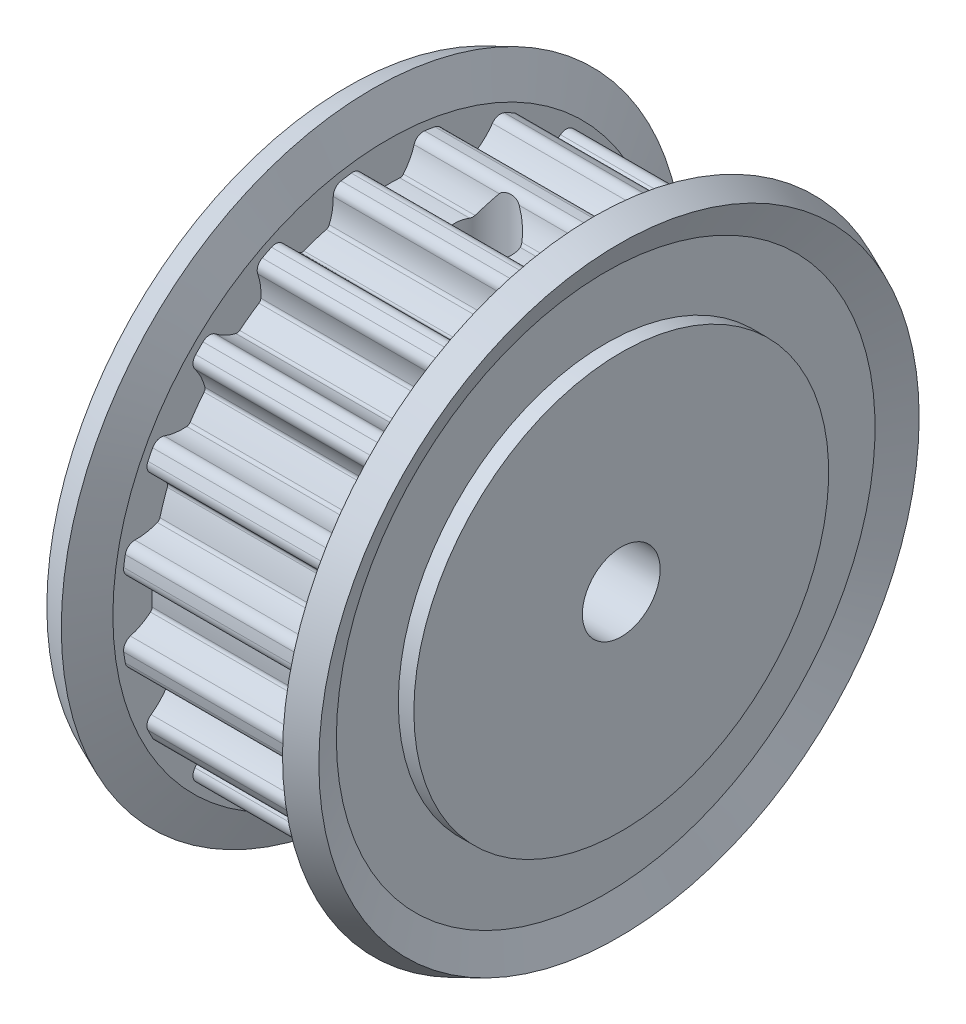
SolidWorks part; units mm, degrees
ref_plane "前视基准面" through (0, 0, 0) normal (0, 0, 1) x (1, 0, 0)
ref_plane "上视基准面" through (0, 0, 0) normal (0, 1, 0) x (1, 0, 0)
ref_plane "右视基准面" through (0, 0, 0) normal (1, 0, 0) x (0, 0, -1)
sketch "草图1" plane through (0, 0, 0) normal (0, 0, 1) x (1, 0, 0)
  line L0 (0, 12) -> (0, 2.25)
  line L1 (0, 2.25) -> (28, 2.25)
  line L2 (28, 2.25) -> (28, 4.175)
  line L3 (28, 4.175) -> (16, 4.175)
  line L4 (16, 4.175) -> (16, 12)
  line L5 (16, 12) -> (15.1, 12)
  line L6 (15.1, 12) -> (15.1, 15.5844)
  line L7 (15.1, 15.5844) -> (15.869, 17.3659)
  line L8 (15.869, 17.3659) -> (14.4, 18)
  line L9 (14.4, 18) -> (13.5, 15.915)
  line L10 (13.5, 15.915) -> (13.5, 15.435)
  line L11 (13.5, 15.435) -> (2.5, 15.435)
  line L12 (2.5, 15.435) -> (2.5, 15.915)
  line L13 (2.5, 15.915) -> (1.6, 18)
  line L14 (1.6, 18) -> (0.131, 17.3659)
  line L15 (0.131, 17.3659) -> (0.9, 15.5844)
  line L16 (0.9, 15.5844) -> (0.9, 12)
  line L17 (0.9, 12) -> (0, 12)
  line L18 (28, 0) -> (0, 0) construction
  dimension "D1" = 2.25
  dimension "D2" = 9.75
revolve "旋转1" add sketch "草图1" angle 360 about L18 reverse direction yes
sketch "草图2" plane through (0, 0, 0) normal (0, 0, 1) x (1, 0, 0)
  line L0 (16, 0) -> (16, 18)
  line L1 (16, 18) -> (32, 18)
  line L2 (32, 18) -> (32, 0)
  line L3 (32, 0) -> (16, 0)
  line L4 (32, 0) -> (16, 0) construction
revolve "切除-旋转1" cut sketch "草图2" angle 360 about L4 reverse direction yes
ref_plane "基准面1" through (2.5, 0, 0) normal (1, 0, 0) x (0, 0, -1)
sketch "草图3" plane through (2.5, 0, 0) normal (1, 0, 0) x (0, 0, -1)
  line L0 (2.1176, 15.2891) -> (2.1176, 20.58)
  line L1 (2.1176, 20.58) -> (-2.1176, 20.58)
  line L2 (-2.1176, 20.58) -> (-2.1176, 15.2891)
  arc A0 (-2.1176, 15.2891) -> (-1.5148, 14.9006) centre (-2.0421, 14.7443) cw
  arc A1 (-1.5148, 14.9006) -> (-0.8928, 13.7375) centre (1.625, 15.8318) ccw
  arc A2 (-0.8928, 13.7375) -> (-0.688, 13.6477) centre (-0.7006, 13.8974) ccw
  arc A3 (-0.688, 13.6477) -> (0.688, 13.6477) centre (0, 0) cw
  arc A4 (0.688, 13.6477) -> (0.8928, 13.7375) centre (0.7006, 13.8974) ccw
  arc A5 (0.8928, 13.7375) -> (1.5148, 14.9006) centre (-1.625, 15.8318) ccw
  arc A6 (1.5148, 14.9006) -> (2.1176, 15.2891) centre (2.0421, 14.7443) cw
extrude "切除-拉伸1" cut sketch "草图3" along normal blind 11
sketch "草图5" plane through (2.5, 0, 0) normal (1, 0, 0) x (0, 0, -1)
  line L0 (-2.7106, 15.1951) -> (-4.3456, 20.2271)
  line L1 (-4.3456, 20.2271) -> (-8.3735, 18.9184)
  line L2 (-8.3735, 18.9184) -> (-6.7385, 13.8864)
  arc A0 (-6.7385, 13.8864) -> (-6.0452, 13.7032) centre (-6.4984, 13.3916) cw
  arc A1 (-6.0452, 13.7032) -> (-5.0942, 12.7892) centre (-3.3468, 15.5591) ccw
  arc A2 (-5.0942, 12.7892) -> (-4.8717, 12.7671) centre (-4.9608, 13.0007) ccw
  arc A3 (-4.8717, 12.7671) -> (-3.563, 13.1923) centre (0, 0) cw
  arc A4 (-3.563, 13.1923) -> (-3.396, 13.341) centre (-3.6282, 13.4337) ccw
  arc A5 (-3.396, 13.341) -> (-3.1639, 14.6395) centre (-6.4378, 14.5548) ccw
  arc A6 (-3.1639, 14.6395) -> (-2.7106, 15.1951) centre (-2.614, 14.6537) cw
sketch "草图6" plane through (2.5, 0, 0) normal (1, 0, 0) x (0, 0, -1)
  line L0 (-7.2735, 13.6138) -> (-10.3835, 17.8943)
  line L1 (-10.3835, 17.8943) -> (-13.8098, 15.4049)
  line L2 (-13.8098, 15.4049) -> (-10.6998, 11.1244)
  arc A0 (-10.6998, 11.1244) -> (-9.9839, 11.1645) centre (-10.3186, 10.728) cw
  arc A1 (-9.9839, 11.1645) -> (-8.797, 10.5891) centre (-7.9911, 13.7634) ccw
  arc A2 (-8.797, 10.5891) -> (-8.5785, 10.6368) centre (-8.7355, 10.8314) ccw
  arc A3 (-8.5785, 10.6368) -> (-7.4653, 11.4456) centre (0, 0) cw
  arc A4 (-7.4653, 11.4456) -> (-7.3524, 11.6386) centre (-7.6019, 11.655) ccw
  arc A5 (-7.3524, 11.6386) -> (-7.5329, 12.9453) centre (-10.6204, 11.8531) ccw
  arc A6 (-7.5329, 12.9453) -> (-7.2735, 13.6138) centre (-7.0143, 13.1287) cw
sketch "草图7" plane through (2.5, 0, 0) normal (1, 0, 0) x (0, 0, -1)
  line L0 (-11.1244, 10.6998) -> (-15.4049, 13.8098)
  line L1 (-15.4049, 13.8098) -> (-17.8943, 10.3835)
  line L2 (-17.8943, 10.3835) -> (-13.6138, 7.2735)
  arc A0 (-13.6138, 7.2735) -> (-12.9453, 7.5329) centre (-13.1287, 7.0143) cw
  arc A1 (-12.9453, 7.5329) -> (-11.6386, 7.3524) centre (-11.8531, 10.6204) ccw
  arc A2 (-11.6386, 7.3524) -> (-11.4456, 7.4653) centre (-11.655, 7.6019) ccw
  arc A3 (-11.4456, 7.4653) -> (-10.6368, 8.5785) centre (0, 0) cw
  arc A4 (-10.6368, 8.5785) -> (-10.5891, 8.797) centre (-10.8314, 8.7355) ccw
  arc A5 (-10.5891, 8.797) -> (-11.1645, 9.9839) centre (-13.7634, 7.9911) ccw
  arc A6 (-11.1645, 9.9839) -> (-11.1244, 10.6998) centre (-10.728, 10.3186) cw
sketch "草图8" plane through (2.5, 0, 0) normal (1, 0, 0) x (0, 0, -1)
  line L0 (-13.8864, 6.7385) -> (-18.9184, 8.3735)
  line L1 (-18.9184, 8.3735) -> (-20.2271, 4.3456)
  line L2 (-20.2271, 4.3456) -> (-15.1951, 2.7106)
  arc A0 (-15.1951, 2.7106) -> (-14.6395, 3.1639) centre (-14.6537, 2.614) cw
  arc A1 (-14.6395, 3.1639) -> (-13.341, 3.396) centre (-14.5548, 6.4378) ccw
  arc A2 (-13.341, 3.396) -> (-13.1923, 3.563) centre (-13.4337, 3.6282) ccw
  arc A3 (-13.1923, 3.563) -> (-12.7671, 4.8717) centre (0, 0) cw
  arc A4 (-12.7671, 4.8717) -> (-12.7892, 5.0942) centre (-13.0007, 4.9608) ccw
  arc A5 (-12.7892, 5.0942) -> (-13.7032, 6.0452) centre (-15.5591, 3.3468) ccw
  arc A6 (-13.7032, 6.0452) -> (-13.8864, 6.7385) centre (-13.3916, 6.4984) cw
sketch "草图9" plane through (2.5, 0, 0) normal (1, 0, 0) x (0, 0, -1)
  line L0 (-15.2891, 2.1176) -> (-20.58, 2.1176)
  line L1 (-20.58, 2.1176) -> (-20.58, -2.1176)
  line L2 (-20.58, -2.1176) -> (-15.2891, -2.1176)
  arc A0 (-15.2891, -2.1176) -> (-14.9006, -1.5148) centre (-14.7443, -2.0421) cw
  arc A1 (-14.9006, -1.5148) -> (-13.7375, -0.8928) centre (-15.8318, 1.625) ccw
  arc A2 (-13.7375, -0.8928) -> (-13.6477, -0.688) centre (-13.8974, -0.7006) ccw
  arc A3 (-13.6477, -0.688) -> (-13.6477, 0.688) centre (0, 0) cw
  arc A4 (-13.6477, 0.688) -> (-13.7375, 0.8928) centre (-13.8974, 0.7006) ccw
  arc A5 (-13.7375, 0.8928) -> (-14.9006, 1.5148) centre (-15.8318, -1.625) ccw
  arc A6 (-14.9006, 1.5148) -> (-15.2891, 2.1176) centre (-14.7443, 2.0421) cw
sketch "草图10" plane through (2.5, 0, 0) normal (1, 0, 0) x (0, 0, -1)
  line L0 (-15.1951, -2.7106) -> (-20.2271, -4.3456)
  line L1 (-20.2271, -4.3456) -> (-18.9184, -8.3735)
  line L2 (-18.9184, -8.3735) -> (-13.8864, -6.7385)
  arc A0 (-13.8864, -6.7385) -> (-13.7032, -6.0452) centre (-13.3916, -6.4984) cw
  arc A1 (-13.7032, -6.0452) -> (-12.7892, -5.0942) centre (-15.5591, -3.3468) ccw
  arc A2 (-12.7892, -5.0942) -> (-12.7671, -4.8717) centre (-13.0007, -4.9608) ccw
  arc A3 (-12.7671, -4.8717) -> (-13.1923, -3.563) centre (0, 0) cw
  arc A4 (-13.1923, -3.563) -> (-13.341, -3.396) centre (-13.4337, -3.6282) ccw
  arc A5 (-13.341, -3.396) -> (-14.6395, -3.1639) centre (-14.5548, -6.4378) ccw
  arc A6 (-14.6395, -3.1639) -> (-15.1951, -2.7106) centre (-14.6537, -2.614) cw
sketch "草图11" plane through (2.5, 0, 0) normal (1, 0, 0) x (0, 0, -1)
  line L0 (-13.6138, -7.2735) -> (-17.8943, -10.3835)
  line L1 (-17.8943, -10.3835) -> (-15.4049, -13.8098)
  line L2 (-15.4049, -13.8098) -> (-11.1244, -10.6998)
  arc A0 (-11.1244, -10.6998) -> (-11.1645, -9.9839) centre (-10.728, -10.3186) cw
  arc A1 (-11.1645, -9.9839) -> (-10.5891, -8.797) centre (-13.7634, -7.9911) ccw
  arc A2 (-10.5891, -8.797) -> (-10.6368, -8.5785) centre (-10.8314, -8.7355) ccw
  arc A3 (-10.6368, -8.5785) -> (-11.4456, -7.4653) centre (0, 0) cw
  arc A4 (-11.4456, -7.4653) -> (-11.6386, -7.3524) centre (-11.655, -7.6019) ccw
  arc A5 (-11.6386, -7.3524) -> (-12.9453, -7.5329) centre (-11.8531, -10.6204) ccw
  arc A6 (-12.9453, -7.5329) -> (-13.6138, -7.2735) centre (-13.1287, -7.0143) cw
sketch "草图12" plane through (2.5, 0, 0) normal (1, 0, 0) x (0, 0, -1)
  line L0 (-10.6998, -11.1244) -> (-13.8098, -15.4049)
  line L1 (-13.8098, -15.4049) -> (-10.3835, -17.8943)
  line L2 (-10.3835, -17.8943) -> (-7.2735, -13.6138)
  arc A0 (-7.2735, -13.6138) -> (-7.5329, -12.9453) centre (-7.0143, -13.1287) cw
  arc A1 (-7.5329, -12.9453) -> (-7.3524, -11.6386) centre (-10.6204, -11.8531) ccw
  arc A2 (-7.3524, -11.6386) -> (-7.4653, -11.4456) centre (-7.6019, -11.655) ccw
  arc A3 (-7.4653, -11.4456) -> (-8.5785, -10.6368) centre (0, 0) cw
  arc A4 (-8.5785, -10.6368) -> (-8.797, -10.5891) centre (-8.7355, -10.8314) ccw
  arc A5 (-8.797, -10.5891) -> (-9.9839, -11.1645) centre (-7.9911, -13.7634) ccw
  arc A6 (-9.9839, -11.1645) -> (-10.6998, -11.1244) centre (-10.3186, -10.728) cw
sketch "草图13" plane through (2.5, 0, 0) normal (1, 0, 0) x (0, 0, -1)
  line L0 (-6.7385, -13.8864) -> (-8.3735, -18.9184)
  line L1 (-8.3735, -18.9184) -> (-4.3456, -20.2271)
  line L2 (-4.3456, -20.2271) -> (-2.7106, -15.1951)
  arc A0 (-2.7106, -15.1951) -> (-3.1639, -14.6395) centre (-2.614, -14.6537) cw
  arc A1 (-3.1639, -14.6395) -> (-3.396, -13.341) centre (-6.4378, -14.5548) ccw
  arc A2 (-3.396, -13.341) -> (-3.563, -13.1923) centre (-3.6282, -13.4337) ccw
  arc A3 (-3.563, -13.1923) -> (-4.8717, -12.7671) centre (0, 0) cw
  arc A4 (-4.8717, -12.7671) -> (-5.0942, -12.7892) centre (-4.9608, -13.0007) ccw
  arc A5 (-5.0942, -12.7892) -> (-6.0452, -13.7032) centre (-3.3468, -15.5591) ccw
  arc A6 (-6.0452, -13.7032) -> (-6.7385, -13.8864) centre (-6.4984, -13.3916) cw
sketch "草图14" plane through (2.5, 0, 0) normal (1, 0, 0) x (0, 0, -1)
  line L0 (-2.1176, -15.2891) -> (-2.1176, -20.58)
  line L1 (-2.1176, -20.58) -> (2.1176, -20.58)
  line L2 (2.1176, -20.58) -> (2.1176, -15.2891)
  arc A0 (2.1176, -15.2891) -> (1.5148, -14.9006) centre (2.0421, -14.7443) cw
  arc A1 (1.5148, -14.9006) -> (0.8928, -13.7375) centre (-1.625, -15.8318) ccw
  arc A2 (0.8928, -13.7375) -> (0.688, -13.6477) centre (0.7006, -13.8974) ccw
  arc A3 (0.688, -13.6477) -> (-0.688, -13.6477) centre (0, 0) cw
  arc A4 (-0.688, -13.6477) -> (-0.8928, -13.7375) centre (-0.7006, -13.8974) ccw
  arc A5 (-0.8928, -13.7375) -> (-1.5148, -14.9006) centre (1.625, -15.8318) ccw
  arc A6 (-1.5148, -14.9006) -> (-2.1176, -15.2891) centre (-2.0421, -14.7443) cw
sketch "草图15" plane through (2.5, 0, 0) normal (1, 0, 0) x (0, 0, -1)
  line L0 (2.7106, -15.1951) -> (4.3456, -20.2271)
  line L1 (4.3456, -20.2271) -> (8.3735, -18.9184)
  line L2 (8.3735, -18.9184) -> (6.7385, -13.8864)
  arc A0 (6.7385, -13.8864) -> (6.0452, -13.7032) centre (6.4984, -13.3916) cw
  arc A1 (6.0452, -13.7032) -> (5.0942, -12.7892) centre (3.3468, -15.5591) ccw
  arc A2 (5.0942, -12.7892) -> (4.8717, -12.7671) centre (4.9608, -13.0007) ccw
  arc A3 (4.8717, -12.7671) -> (3.563, -13.1923) centre (0, 0) cw
  arc A4 (3.563, -13.1923) -> (3.396, -13.341) centre (3.6282, -13.4337) ccw
  arc A5 (3.396, -13.341) -> (3.1639, -14.6395) centre (6.4378, -14.5548) ccw
  arc A6 (3.1639, -14.6395) -> (2.7106, -15.1951) centre (2.614, -14.6537) cw
sketch "草图16" plane through (2.5, 0, 0) normal (1, 0, 0) x (0, 0, -1)
  line L0 (7.2735, -13.6138) -> (10.3835, -17.8943)
  line L1 (10.3835, -17.8943) -> (13.8098, -15.4049)
  line L2 (13.8098, -15.4049) -> (10.6998, -11.1244)
  arc A0 (10.6998, -11.1244) -> (9.9839, -11.1645) centre (10.3186, -10.728) cw
  arc A1 (9.9839, -11.1645) -> (8.797, -10.5891) centre (7.9911, -13.7634) ccw
  arc A2 (8.797, -10.5891) -> (8.5785, -10.6368) centre (8.7355, -10.8314) ccw
  arc A3 (8.5785, -10.6368) -> (7.4653, -11.4456) centre (0, 0) cw
  arc A4 (7.4653, -11.4456) -> (7.3524, -11.6386) centre (7.6019, -11.655) ccw
  arc A5 (7.3524, -11.6386) -> (7.5329, -12.9453) centre (10.6204, -11.8531) ccw
  arc A6 (7.5329, -12.9453) -> (7.2735, -13.6138) centre (7.0143, -13.1287) cw
sketch "草图17" plane through (2.5, 0, 0) normal (1, 0, 0) x (0, 0, -1)
  line L0 (11.1244, -10.6998) -> (15.4049, -13.8098)
  line L1 (15.4049, -13.8098) -> (17.8943, -10.3835)
  line L2 (17.8943, -10.3835) -> (13.6138, -7.2735)
  arc A0 (13.6138, -7.2735) -> (12.9453, -7.5329) centre (13.1287, -7.0143) cw
  arc A1 (12.9453, -7.5329) -> (11.6386, -7.3524) centre (11.8531, -10.6204) ccw
  arc A2 (11.6386, -7.3524) -> (11.4456, -7.4653) centre (11.655, -7.6019) ccw
  arc A3 (11.4456, -7.4653) -> (10.6368, -8.5785) centre (0, 0) cw
  arc A4 (10.6368, -8.5785) -> (10.5891, -8.797) centre (10.8314, -8.7355) ccw
  arc A5 (10.5891, -8.797) -> (11.1645, -9.9839) centre (13.7634, -7.9911) ccw
  arc A6 (11.1645, -9.9839) -> (11.1244, -10.6998) centre (10.728, -10.3186) cw
sketch "草图18" plane through (2.5, 0, 0) normal (1, 0, 0) x (0, 0, -1)
  line L0 (13.8864, -6.7385) -> (18.9184, -8.3735)
  line L1 (18.9184, -8.3735) -> (20.2271, -4.3456)
  line L2 (20.2271, -4.3456) -> (15.1951, -2.7106)
  arc A0 (15.1951, -2.7106) -> (14.6395, -3.1639) centre (14.6537, -2.614) cw
  arc A1 (14.6395, -3.1639) -> (13.341, -3.396) centre (14.5548, -6.4378) ccw
  arc A2 (13.341, -3.396) -> (13.1923, -3.563) centre (13.4337, -3.6282) ccw
  arc A3 (13.1923, -3.563) -> (12.7671, -4.8717) centre (0, 0) cw
  arc A4 (12.7671, -4.8717) -> (12.7892, -5.0942) centre (13.0007, -4.9608) ccw
  arc A5 (12.7892, -5.0942) -> (13.7032, -6.0452) centre (15.5591, -3.3468) ccw
  arc A6 (13.7032, -6.0452) -> (13.8864, -6.7385) centre (13.3916, -6.4984) cw
sketch "草图19" plane through (2.5, 0, 0) normal (1, 0, 0) x (0, 0, -1)
  line L0 (15.2891, -2.1176) -> (20.58, -2.1176)
  line L1 (20.58, -2.1176) -> (20.58, 2.1176)
  line L2 (20.58, 2.1176) -> (15.2891, 2.1176)
  arc A0 (15.2891, 2.1176) -> (14.9006, 1.5148) centre (14.7443, 2.0421) cw
  arc A1 (14.9006, 1.5148) -> (13.7375, 0.8928) centre (15.8318, -1.625) ccw
  arc A2 (13.7375, 0.8928) -> (13.6477, 0.688) centre (13.8974, 0.7006) ccw
  arc A3 (13.6477, 0.688) -> (13.6477, -0.688) centre (0, 0) cw
  arc A4 (13.6477, -0.688) -> (13.7375, -0.8928) centre (13.8974, -0.7006) ccw
  arc A5 (13.7375, -0.8928) -> (14.9006, -1.5148) centre (15.8318, 1.625) ccw
  arc A6 (14.9006, -1.5148) -> (15.2891, -2.1176) centre (14.7443, -2.0421) cw
sketch "草图20" plane through (2.5, 0, 0) normal (1, 0, 0) x (0, 0, -1)
  line L0 (15.1951, 2.7106) -> (20.2271, 4.3456)
  line L1 (20.2271, 4.3456) -> (18.9184, 8.3735)
  line L2 (18.9184, 8.3735) -> (13.8864, 6.7385)
  arc A0 (13.8864, 6.7385) -> (13.7032, 6.0452) centre (13.3916, 6.4984) cw
  arc A1 (13.7032, 6.0452) -> (12.7892, 5.0942) centre (15.5591, 3.3468) ccw
  arc A2 (12.7892, 5.0942) -> (12.7671, 4.8717) centre (13.0007, 4.9608) ccw
  arc A3 (12.7671, 4.8717) -> (13.1923, 3.563) centre (0, 0) cw
  arc A4 (13.1923, 3.563) -> (13.341, 3.396) centre (13.4337, 3.6282) ccw
  arc A5 (13.341, 3.396) -> (14.6395, 3.1639) centre (14.5548, 6.4378) ccw
  arc A6 (14.6395, 3.1639) -> (15.1951, 2.7106) centre (14.6537, 2.614) cw
sketch "草图21" plane through (2.5, 0, 0) normal (1, 0, 0) x (0, 0, -1)
  line L0 (13.6138, 7.2735) -> (17.8943, 10.3835)
  line L1 (17.8943, 10.3835) -> (15.4049, 13.8098)
  line L2 (15.4049, 13.8098) -> (11.1244, 10.6998)
  arc A0 (11.1244, 10.6998) -> (11.1645, 9.9839) centre (10.728, 10.3186) cw
  arc A1 (11.1645, 9.9839) -> (10.5891, 8.797) centre (13.7634, 7.9911) ccw
  arc A2 (10.5891, 8.797) -> (10.6368, 8.5785) centre (10.8314, 8.7355) ccw
  arc A3 (10.6368, 8.5785) -> (11.4456, 7.4653) centre (0, 0) cw
  arc A4 (11.4456, 7.4653) -> (11.6386, 7.3524) centre (11.655, 7.6019) ccw
  arc A5 (11.6386, 7.3524) -> (12.9453, 7.5329) centre (11.8531, 10.6204) ccw
  arc A6 (12.9453, 7.5329) -> (13.6138, 7.2735) centre (13.1287, 7.0143) cw
sketch "草图22" plane through (2.5, 0, 0) normal (1, 0, 0) x (0, 0, -1)
  line L0 (10.6998, 11.1244) -> (13.8098, 15.4049)
  line L1 (13.8098, 15.4049) -> (10.3835, 17.8943)
  line L2 (10.3835, 17.8943) -> (7.2735, 13.6138)
  arc A0 (7.2735, 13.6138) -> (7.5329, 12.9453) centre (7.0143, 13.1287) cw
  arc A1 (7.5329, 12.9453) -> (7.3524, 11.6386) centre (10.6204, 11.8531) ccw
  arc A2 (7.3524, 11.6386) -> (7.4653, 11.4456) centre (7.6019, 11.655) ccw
  arc A3 (7.4653, 11.4456) -> (8.5785, 10.6368) centre (0, 0) cw
  arc A4 (8.5785, 10.6368) -> (8.797, 10.5891) centre (8.7355, 10.8314) ccw
  arc A5 (8.797, 10.5891) -> (9.9839, 11.1645) centre (7.9911, 13.7634) ccw
  arc A6 (9.9839, 11.1645) -> (10.6998, 11.1244) centre (10.3186, 10.728) cw
sketch "草图23" plane through (2.5, 0, 0) normal (1, 0, 0) x (0, 0, -1)
  line L0 (6.7385, 13.8864) -> (8.3735, 18.9184)
  line L1 (8.3735, 18.9184) -> (4.3456, 20.2271)
  line L2 (4.3456, 20.2271) -> (2.7106, 15.1951)
  arc A0 (2.7106, 15.1951) -> (3.1639, 14.6395) centre (2.614, 14.6537) cw
  arc A1 (3.1639, 14.6395) -> (3.396, 13.341) centre (6.4378, 14.5548) ccw
  arc A2 (3.396, 13.341) -> (3.563, 13.1923) centre (3.6282, 13.4337) ccw
  arc A3 (3.563, 13.1923) -> (4.8717, 12.7671) centre (0, 0) cw
  arc A4 (4.8717, 12.7671) -> (5.0942, 12.7892) centre (4.9608, 13.0007) ccw
  arc A5 (5.0942, 12.7892) -> (6.0452, 13.7032) centre (3.3468, 15.5591) ccw
  arc A6 (6.0452, 13.7032) -> (6.7385, 13.8864) centre (6.4984, 13.3916) cw
extrude "切除-拉伸2" cut sketch "草图5" along normal blind 11
extrude "切除-拉伸3" cut sketch "草图6" along normal blind 11
extrude "切除-拉伸4" cut sketch "草图7" along normal blind 11
extrude "切除-拉伸5" cut sketch "草图8" along normal blind 11
extrude "切除-拉伸6" cut sketch "草图9" along normal blind 11
extrude "切除-拉伸7" cut sketch "草图10" along normal blind 11
extrude "切除-拉伸8" cut sketch "草图11" along normal blind 11
extrude "切除-拉伸9" cut sketch "草图12" along normal blind 11
extrude "切除-拉伸10" cut sketch "草图13" along normal blind 11
extrude "切除-拉伸11" cut sketch "草图14" along normal blind 11
extrude "切除-拉伸12" cut sketch "草图15" along normal blind 11
extrude "切除-拉伸13" cut sketch "草图16" along normal blind 11
extrude "切除-拉伸14" cut sketch "草图17" along normal blind 11
extrude "切除-拉伸15" cut sketch "草图18" along normal blind 11
extrude "切除-拉伸16" cut sketch "草图19" along normal blind 11
extrude "切除-拉伸17" cut sketch "草图20" along normal blind 11
extrude "切除-拉伸18" cut sketch "草图21" along normal blind 11
extrude "切除-拉伸19" cut sketch "草图22" along normal blind 11
extrude "切除-拉伸20" cut sketch "草图23" along normal blind 11
ref_plane "基准面2" through (8, 0, 0) normal (1, 0, 0) x (0, 0, -1)
sketch "草图24" plane through (8, 0, 0) normal (1, 0, 0) x (0, 0, -1)
  line L0 (0, 15.435) -> (1.621, 15.435)
  line L1 (1.621, 15.435) -> (1.621, 2.675)
  line L2 (1.621, 2.675) -> (0, 2.675)
  line L3 (0, 2.675) -> (0, 15.435)
  line L4 (0, 2.675) -> (0, 15.435) construction
revolve "切除-旋转2" cut sketch "草图24" angle 360 about L4 reverse direction yes
sketch "草图25" plane through (8, 0, 0) normal (1, 0, 0) x (0, 0, -1)
  line L0 (12.4872, -9.0725) -> (11.5344, -10.3839)
  line L1 (11.5344, -10.3839) -> (-0.9528, -1.3114)
  line L2 (-0.9528, -1.3114) -> (0, 0)
  line L3 (0, 0) -> (12.4872, -9.0725)
  line L4 (0, 0) -> (12.4872, -9.0725) construction
revolve "切除-旋转3" cut sketch "草图25" angle 360 about L4 reverse direction yes
ref_plane "基准面3" through (0, 0, 0) normal (0, 0.866, 0.5) x (1, 0, 0)
ref_plane "基准面4" through (0, 0, 0) normal (0, -0.5, 0.866) x (1, 0, 0)
ref_plane "基准面5" through (16, 0, 0) normal (1, 0, 0) x (0, 0, -1)
ref_plane "基准面6" through (0, 0, 0) normal (0, 1, 0) x (1, 0, 0)
ref_plane "基准面7" through (0, 0, 0) normal (0, 0, -1) x (-1, 0, 0)
ref_plane "基准面8" through (0, 0, 0) normal (0, 1, 0) x (1, 0, 0)
ref_plane "基准面9" through (0, 15.435, 0) normal (0, 1, 0) x (1, 0, 0)
ref_plane "基准面10" through (0, 0, 0) normal (0, -0.5878, -0.809) x (-1, 0, 0)
ref_plane "基准面11" through (0, -9.0725, -12.4872) normal (0, -0.5878, -0.809) x (-1, 0, 0)
ref_plane "基准面12" through (8, 0, 0) normal (1, 0, 0) x (0, 0, -1)
ref_plane "to_s1 XY" through (0, 15.435, 0) normal (0, 1, 0) x (1, 0, 0)
ref_plane "to_s1 XZ" through (0, 0, 0) normal (0, 0, 1) x (1, 0, 0)
ref_plane "to_s1 YZ" through (8, 0, 0) normal (1, 0, 0) x (0, 0, -1)
ref_axis "to_s1 X" through (-80.9, 15.435, 0) along (1, 0, 0)
ref_axis "to_s1 Y" through (8, 15.435, 50) along (0, 0, -1)
ref_axis "to_s1 Z" through (8, 50, 0) along (0, -1, 0)
sketch3d "to_s1"
  point P0 (8, 15.435, 0)
ref_plane "to_s2 XY" through (0, -9.0725, -12.4872) normal (0, -0.5878, -0.809) x (-1, 0, 0)
ref_plane "to_s2 XZ" through (0, 0, 0) normal (0, 0.809, -0.5878) x (1, 0, 0)
ref_plane "to_s2 YZ" through (8, 0, 0) normal (1, 0, 0) x (0, 0, -1)
ref_axis "to_s2 X" through (-80.9, -9.0725, -12.4872) along (1, 0, 0)
ref_axis "to_s2 Y" through (8, 31.3784, -41.8764) along (0, -0.809, 0.5878)
ref_axis "to_s2 Z" through (8, -50, -68.8191) along (0, 0.5878, 0.809)
sketch3d "to_s2"
  point P0 (8, -9.0725, -12.4872)
ref_plane "C1 XY" through (8, 0, 0) normal (1, 0, 0) x (0, 0, -1)
ref_plane "C1 XZ" through (0, 0, 0) normal (0, -1, 0) x (-1, 0, 0)
ref_plane "C1 YZ" through (0, 0, 0) normal (0, 0, -1) x (-1, 0, 0)
ref_axis "C1 X" through (8, 0, 80.9) along (0, 0, -1)
ref_axis "C1 Y" through (8, -50, 0) along (0, 1, 0)
ref_axis "C1 Z" through (80.9, 0, 0) along (-1, 0, 0)
sketch3d "C1"
  point P0 (8, 0, 0)
